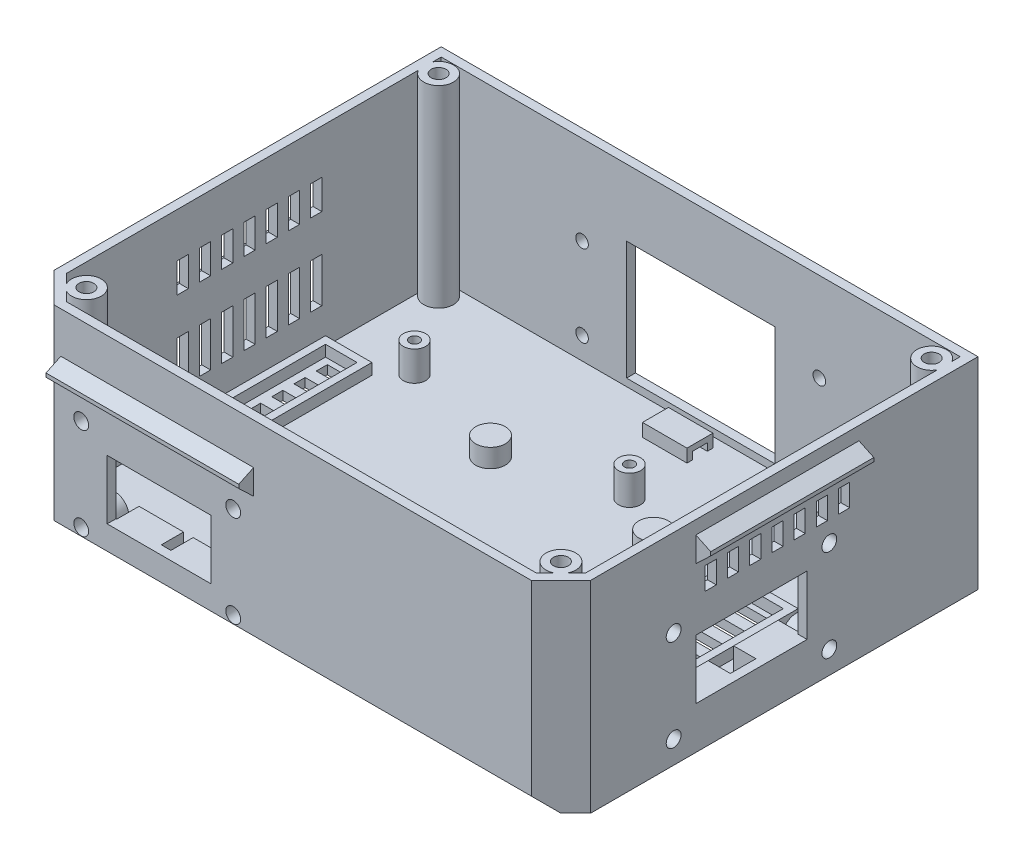
SolidWorks part; units mm, degrees
ref_plane "Front Plane" through (0, 0, 0) normal (0, 0, 1) x (1, 0, 0)
ref_plane "Top Plane" through (0, 0, 0) normal (0, 1, 0) x (1, 0, 0)
ref_plane "Right Plane" through (0, 0, 0) normal (1, 0, 0) x (0, 0, -1)
ref_plane "PZm28_4" through (0, -28.4, 0) normal (0, 1, 0) x (1, 0, 0)
sketch "Sketch1" plane through (0, -28.4, 0) normal (0, 1, 0) x (1, 0, 0)
  line L0 (-64.4, -124.4) -> (64.4, -124.4)
  line L1 (64.4, -124.4) -> (72.4, -116.4)
  line L2 (72.4, -116.4) -> (72.4, -11.9)
  line L3 (72.4, -11.9) -> (-72.4, -11.9)
  line L4 (-72.4, -11.9) -> (-72.4, -116.4)
  line L5 (-72.4, -116.4) -> (-64.4, -124.4)
extrude "Box Block" add sketch "Sketch1" along normal blind 54.4
sketch "Sketch2" plane through (0, 0, 0) normal (1, 0, 0) x (0, 0, -1)
  line L0 (-125.4, -23.4) -> (-119.4, -29.4)
  line L1 (-119.4, -29.4) -> (-125.4, -29.4)
  line L2 (-125.4, -29.4) -> (-125.4, -23.4)
extrude "Rear Bottom Facet" cut sketch "Sketch2" against normal through all and the other way through all
shell "Shell" thickness 2.4 removed face at (0, 26, 84.2333)
ref_plane "PY11_4" through (0, 0, 11.4) normal (0, 0, 1) x (1, 0, 0)
sketch "Sketch3" plane through (0, 0, 11.4) normal (0, 0, 1) x (1, 0, 0)
  line L0 (-20, -24) -> (20, -24)
  line L1 (20, -24) -> (20, 8)
  line L2 (20, 8) -> (-20, 8)
  line L3 (-20, 8) -> (-20, -24)
  circle A0 centre (-32, 2) radius 1.7
  circle A1 centre (32, 2) radius 1.7
  circle A2 centre (-32, -20) radius 1.7
  circle A3 centre (32, -20) radius 1.7
extrude "Cable Window and Flange Holes" cut sketch "Sketch3" along normal blind 3.4
ref_plane "PZm26_5" through (0, -26.5, 0) normal (0, 1, 0) x (1, 0, 0)
sketch "Sketch4" plane through (0, -26.5, 0) normal (0, 1, 0) x (1, 0, 0)
  circle A0 centre (-51.5, -89) radius 3
  circle A1 centre (6.5, -89) radius 3
  circle A2 centre (-51.5, -40) radius 3
  circle A3 centre (6.5, -40) radius 3
extrude "Pi Standoffs" add sketch "Sketch4" along normal blind 8.5
ref_plane "PZm28_9" through (0, -28.9, 0) normal (0, 1, 0) x (1, 0, 0)
sketch "Sketch5" plane through (0, -28.9, 0) normal (0, 1, 0) x (1, 0, 0)
  circle A0 centre (-51.5, -89) radius 1.35
  circle A1 centre (6.5, -89) radius 1.35
  circle A2 centre (-51.5, -40) radius 1.35
  circle A3 centre (6.5, -40) radius 1.35
extrude "Pi Screw Holes" cut sketch "Sketch5" along normal blind 11.4
sketch "Sketch6" plane through (0, -28.9, 0) normal (0, 1, 0) x (1, 0, 0)
  circle A0 centre (-51.5, -89) radius 2.75
  circle A1 centre (6.5, -89) radius 2.75
  circle A2 centre (-51.5, -40) radius 2.75
  circle A3 centre (6.5, -40) radius 2.75
extrude "Pi Counterbores" cut sketch "Sketch6" along normal blind 2.7
sketch "Sketch7" plane through (0, -26.5, 0) normal (0, 1, 0) x (1, 0, 0)
  circle A0 centre (-66.5, -18.5) radius 4
extrude "Lid Boss 1" add sketch "Sketch7" along normal blind 52.5
sketch "Sketch8" plane through (0, -26.5, 0) normal (0, 1, 0) x (1, 0, 0)
  circle A0 centre (66.5, -18.5) radius 4
extrude "Lid Boss 2" add sketch "Sketch8" along normal blind 52.5
sketch "Sketch9" plane through (0, -26.5, 0) normal (0, 1, 0) x (1, 0, 0)
  circle A0 centre (-64, -116) radius 4
extrude "Lid Boss 3" add sketch "Sketch9" along normal blind 52.5
sketch "Sketch10" plane through (0, -26.5, 0) normal (0, 1, 0) x (1, 0, 0)
  circle A0 centre (64, -116) radius 4
extrude "Lid Boss 4" add sketch "Sketch10" along normal blind 52.5
ref_plane "PZ20" through (0, 20, 0) normal (0, 1, 0) x (1, 0, 0)
sketch "Sketch11" plane through (0, 20, 0) normal (0, 1, 0) x (1, 0, 0)
  circle A0 centre (-66.5, -18.5) radius 2
  circle A1 centre (66.5, -18.5) radius 2
  circle A2 centre (-64, -116) radius 2
  circle A3 centre (64, -116) radius 2
extrude "Lid Insert Holes" cut sketch "Sketch11" along normal blind 6.5
sketch "Sketch12" plane through (0, -26.5, 0) normal (0, 1, 0) x (1, 0, 0)
  line L0 (38, -86) -> (58, -86)
  line L1 (58, -86) -> (58, -46)
  line L2 (58, -46) -> (38, -46)
  line L3 (38, -46) -> (38, -86)
  line L4 (40, -84) -> (56, -84)
  line L5 (56, -84) -> (56, -48)
  line L6 (56, -48) -> (40, -48)
  line L7 (40, -48) -> (40, -84)
extrude "Intake Upstand" add sketch "Sketch12" along normal blind 3.5
ref_plane "PZm29_4" through (0, -29.4, 0) normal (0, 1, 0) x (1, 0, 0)
sketch "Sketch13" plane through (0, -29.4, 0) normal (0, 1, 0) x (1, 0, 0)
  line L0 (42, -82.5) -> (54, -82.5)
  line L1 (54, -82.5) -> (54, -79.5)
  line L2 (54, -79.5) -> (42, -79.5)
  line L3 (42, -79.5) -> (42, -82.5)
  line L4 (42, -76.5) -> (54, -76.5)
  line L5 (54, -76.5) -> (54, -73.5)
  line L6 (54, -73.5) -> (42, -73.5)
  line L7 (42, -73.5) -> (42, -76.5)
  line L8 (42, -70.5) -> (54, -70.5)
  line L9 (54, -70.5) -> (54, -67.5)
  line L10 (54, -67.5) -> (42, -67.5)
  line L11 (42, -67.5) -> (42, -70.5)
  line L12 (42, -64.5) -> (54, -64.5)
  line L13 (54, -64.5) -> (54, -61.5)
  line L14 (54, -61.5) -> (42, -61.5)
  line L15 (42, -61.5) -> (42, -64.5)
  line L16 (42, -58.5) -> (54, -58.5)
  line L17 (54, -58.5) -> (54, -55.5)
  line L18 (54, -55.5) -> (42, -55.5)
  line L19 (42, -55.5) -> (42, -58.5)
  line L20 (42, -52.5) -> (54, -52.5)
  line L21 (54, -52.5) -> (54, -49.5)
  line L22 (54, -49.5) -> (42, -49.5)
  line L23 (42, -49.5) -> (42, -52.5)
extrude "Intake Slots" cut sketch "Sketch13" along normal blind 3.9
sketch "Sketch14" plane through (0, -26.5, 0) normal (0, 1, 0) x (1, 0, 0)
  line L0 (-69.5, -86) -> (-57, -86)
  line L1 (-57, -86) -> (-57, -46)
  line L2 (-57, -46) -> (-69.5, -46)
  line L3 (-69.5, -46) -> (-69.5, -86)
  line L4 (-67.5, -84) -> (-59, -84)
  line L5 (-59, -84) -> (-59, -48)
  line L6 (-59, -48) -> (-67.5, -48)
  line L7 (-67.5, -48) -> (-67.5, -84)
extrude "Floor Exhaust Upstand" add sketch "Sketch14" along normal blind 3.5
sketch "Sketch15" plane through (0, -29.4, 0) normal (0, 1, 0) x (1, 0, 0)
  line L0 (-65.5, -82.5) -> (-61, -82.5)
  line L1 (-61, -82.5) -> (-61, -79.5)
  line L2 (-61, -79.5) -> (-65.5, -79.5)
  line L3 (-65.5, -79.5) -> (-65.5, -82.5)
  line L4 (-65.5, -76.5) -> (-61, -76.5)
  line L5 (-61, -76.5) -> (-61, -73.5)
  line L6 (-61, -73.5) -> (-65.5, -73.5)
  line L7 (-65.5, -73.5) -> (-65.5, -76.5)
  line L8 (-65.5, -70.5) -> (-61, -70.5)
  line L9 (-61, -70.5) -> (-61, -67.5)
  line L10 (-61, -67.5) -> (-65.5, -67.5)
  line L11 (-65.5, -67.5) -> (-65.5, -70.5)
  line L12 (-65.5, -64.5) -> (-61, -64.5)
  line L13 (-61, -64.5) -> (-61, -61.5)
  line L14 (-61, -61.5) -> (-65.5, -61.5)
  line L15 (-65.5, -61.5) -> (-65.5, -64.5)
  line L16 (-65.5, -58.5) -> (-61, -58.5)
  line L17 (-61, -58.5) -> (-61, -55.5)
  line L18 (-61, -55.5) -> (-65.5, -55.5)
  line L19 (-65.5, -55.5) -> (-65.5, -58.5)
  line L20 (-65.5, -52.5) -> (-61, -52.5)
  line L21 (-61, -52.5) -> (-61, -49.5)
  line L22 (-61, -49.5) -> (-65.5, -49.5)
  line L23 (-65.5, -49.5) -> (-65.5, -52.5)
extrude "Floor Exhaust Slots" cut sketch "Sketch15" along normal blind 3.9
ref_plane "PXm72_9" through (-72.9, 0, 0) normal (1, 0, 0) x (0, 0, -1)
sketch "Sketch16" plane through (-72.9, 0, 0) normal (1, 0, 0) x (0, 0, -1)
  line L0 (-85.5, -16) -> (-82.5, -16)
  line L1 (-82.5, -16) -> (-82.5, -4)
  line L2 (-82.5, -4) -> (-85.5, -4)
  line L3 (-85.5, -4) -> (-85.5, -16)
  line L4 (-79.5, -16) -> (-76.5, -16)
  line L5 (-76.5, -16) -> (-76.5, -4)
  line L6 (-76.5, -4) -> (-79.5, -4)
  line L7 (-79.5, -4) -> (-79.5, -16)
  line L8 (-73.5, -16) -> (-70.5, -16)
  line L9 (-70.5, -16) -> (-70.5, -4)
  line L10 (-70.5, -4) -> (-73.5, -4)
  line L11 (-73.5, -4) -> (-73.5, -16)
  line L12 (-67.5, -16) -> (-64.5, -16)
  line L13 (-64.5, -16) -> (-64.5, -4)
  line L14 (-64.5, -4) -> (-67.5, -4)
  line L15 (-67.5, -4) -> (-67.5, -16)
  line L16 (-61.5, -16) -> (-58.5, -16)
  line L17 (-58.5, -16) -> (-58.5, -4)
  line L18 (-58.5, -4) -> (-61.5, -4)
  line L19 (-61.5, -4) -> (-61.5, -16)
  line L20 (-55.5, -16) -> (-52.5, -16)
  line L21 (-52.5, -16) -> (-52.5, -4)
  line L22 (-52.5, -4) -> (-55.5, -4)
  line L23 (-55.5, -4) -> (-55.5, -16)
  line L24 (-49.5, -16) -> (-46.5, -16)
  line L25 (-46.5, -16) -> (-46.5, -4)
  line L26 (-46.5, -4) -> (-49.5, -4)
  line L27 (-49.5, -4) -> (-49.5, -16)
extrude "Exhaust Vents" cut sketch "Sketch16" along normal blind 3.4
ref_plane "PY44" through (0, 0, 44) normal (0, 0, 1) x (1, 0, 0)
sketch "Sketch17" plane through (0, 0, 44) normal (0, 0, 1) x (1, 0, 0)
  line L0 (-72.2, -2.5) -> (-76.4, 1.5)
  line L1 (-76.4, 1.5) -> (-76.4, 2.5)
  line L2 (-76.4, 2.5) -> (-72.2, 4.5)
  line L3 (-72.2, 4.5) -> (-72.2, -2.5)
extrude "Exhaust Drip Ledge" add sketch "Sketch17" along normal blind 44
sketch "Sketch18" plane through (-72.9, 0, 0) normal (1, 0, 0) x (0, 0, -1)
  line L0 (-85.5, 6) -> (-82.5, 6)
  line L1 (-82.5, 6) -> (-82.5, 14)
  line L2 (-82.5, 14) -> (-85.5, 14)
  line L3 (-85.5, 14) -> (-85.5, 6)
  line L4 (-79.5, 6) -> (-76.5, 6)
  line L5 (-76.5, 6) -> (-76.5, 14)
  line L6 (-76.5, 14) -> (-79.5, 14)
  line L7 (-79.5, 14) -> (-79.5, 6)
  line L8 (-73.5, 6) -> (-70.5, 6)
  line L9 (-70.5, 6) -> (-70.5, 14)
  line L10 (-70.5, 14) -> (-73.5, 14)
  line L11 (-73.5, 14) -> (-73.5, 6)
  line L12 (-67.5, 6) -> (-64.5, 6)
  line L13 (-64.5, 6) -> (-64.5, 14)
  line L14 (-64.5, 14) -> (-67.5, 14)
  line L15 (-67.5, 14) -> (-67.5, 6)
  line L16 (-61.5, 6) -> (-58.5, 6)
  line L17 (-58.5, 6) -> (-58.5, 14)
  line L18 (-58.5, 14) -> (-61.5, 14)
  line L19 (-61.5, 14) -> (-61.5, 6)
  line L20 (-55.5, 6) -> (-52.5, 6)
  line L21 (-52.5, 6) -> (-52.5, 14)
  line L22 (-52.5, 14) -> (-55.5, 14)
  line L23 (-55.5, 14) -> (-55.5, 6)
  line L24 (-49.5, 6) -> (-46.5, 6)
  line L25 (-46.5, 6) -> (-46.5, 14)
  line L26 (-46.5, 14) -> (-49.5, 14)
  line L27 (-49.5, 14) -> (-49.5, 6)
extrude "Upper Vents L" cut sketch "Sketch18" along normal blind 3.4
sketch "Sketch19" plane through (0, 0, 44) normal (0, 0, 1) x (1, 0, 0)
  line L0 (-72.2, 15.5) -> (-76.4, 19.5)
  line L1 (-76.4, 19.5) -> (-76.4, 20.5)
  line L2 (-76.4, 20.5) -> (-72.2, 22.5)
  line L3 (-72.2, 22.5) -> (-72.2, 15.5)
extrude "Upper Drip Ledge L" add sketch "Sketch19" along normal blind 44
ref_plane "PX69_5" through (69.5, 0, 0) normal (1, 0, 0) x (0, 0, -1)
sketch "Sketch20" plane through (69.5, 0, 0) normal (1, 0, 0) x (0, 0, -1)
  line L0 (-85.5, 8) -> (-82.5, 8)
  line L1 (-82.5, 8) -> (-82.5, 14)
  line L2 (-82.5, 14) -> (-85.5, 14)
  line L3 (-85.5, 14) -> (-85.5, 8)
  line L4 (-79.5, 8) -> (-76.5, 8)
  line L5 (-76.5, 8) -> (-76.5, 14)
  line L6 (-76.5, 14) -> (-79.5, 14)
  line L7 (-79.5, 14) -> (-79.5, 8)
  line L8 (-73.5, 8) -> (-70.5, 8)
  line L9 (-70.5, 8) -> (-70.5, 14)
  line L10 (-70.5, 14) -> (-73.5, 14)
  line L11 (-73.5, 14) -> (-73.5, 8)
  line L12 (-67.5, 8) -> (-64.5, 8)
  line L13 (-64.5, 8) -> (-64.5, 14)
  line L14 (-64.5, 14) -> (-67.5, 14)
  line L15 (-67.5, 14) -> (-67.5, 8)
  line L16 (-61.5, 8) -> (-58.5, 8)
  line L17 (-58.5, 8) -> (-58.5, 14)
  line L18 (-58.5, 14) -> (-61.5, 14)
  line L19 (-61.5, 14) -> (-61.5, 8)
  line L20 (-55.5, 8) -> (-52.5, 8)
  line L21 (-52.5, 8) -> (-52.5, 14)
  line L22 (-52.5, 14) -> (-55.5, 14)
  line L23 (-55.5, 14) -> (-55.5, 8)
  line L24 (-49.5, 8) -> (-46.5, 8)
  line L25 (-46.5, 8) -> (-46.5, 14)
  line L26 (-46.5, 14) -> (-49.5, 14)
  line L27 (-49.5, 14) -> (-49.5, 8)
extrude "Upper Vents R" cut sketch "Sketch20" along normal blind 3.4
sketch "Sketch21" plane through (0, 0, 44) normal (0, 0, 1) x (1, 0, 0)
  line L0 (72.2, 15.5) -> (76.4, 19.5)
  line L1 (76.4, 19.5) -> (76.4, 20.5)
  line L2 (76.4, 20.5) -> (72.2, 22.5)
  line L3 (72.2, 22.5) -> (72.2, 15.5)
extrude "Upper Drip Ledge R" add sketch "Sketch21" along normal blind 44
ref_plane "PY121_5" through (0, 0, 121.5) normal (0, 0, 1) x (1, 0, 0)
sketch "Sketch22" plane through (0, 0, 121.5) normal (0, 0, 1) x (1, 0, 0)
  line L0 (-50, -18) -> (-22, -18)
  line L1 (-22, -18) -> (-22, -2)
  line L2 (-22, -2) -> (-50, -2)
  line L3 (-50, -2) -> (-50, -18)
extrude "Rear Port Opening" cut sketch "Sketch22" along normal blind 3.4
ref_plane "PY115_5" through (0, 0, 115.5) normal (0, 0, 1) x (1, 0, 0)
sketch "Sketch23" plane through (0, 0, 115.5) normal (0, 0, 1) x (1, 0, 0)
  circle A0 centre (-57, -22.3) radius 4
  circle A1 centre (-57, 2.5) radius 4
  circle A2 centre (-16, -22.3) radius 4
  circle A3 centre (-16, 2.5) radius 4
extrude "Rear Port Bosses" add sketch "Sketch23" along normal blind 6.6
ref_plane "PY117_9" through (0, 0, 117.9) normal (0, 0, 1) x (1, 0, 0)
sketch "Sketch24" plane through (0, 0, 117.9) normal (0, 0, 1) x (1, 0, 0)
  circle A0 centre (-57, -22.3) radius 2
  circle A1 centre (-57, 2.5) radius 2
  circle A2 centre (-16, -22.3) radius 2
  circle A3 centre (-16, 2.5) radius 2
extrude "Rear Port Insert Holes" cut sketch "Sketch24" along normal blind 7
ref_plane "PXm62_5" through (-62.5, 0, 0) normal (1, 0, 0) x (0, 0, -1)
sketch "Sketch25" plane through (-62.5, 0, 0) normal (1, 0, 0) x (0, 0, -1)
  line L0 (-124.2, 8) -> (-128.4, 12)
  line L1 (-128.4, 12) -> (-128.4, 13)
  line L2 (-128.4, 13) -> (-124.2, 15)
  line L3 (-124.2, 15) -> (-124.2, 8)
extrude "Rear Port Drip Ledge" add sketch "Sketch25" along normal blind 52
sketch "Sketch26" plane through (0, -26.5, 0) normal (0, 1, 0) x (1, 0, 0)
  line L0 (-49.8, -122.1) -> (-37.8, -122.1)
  line L1 (-37.8, -122.1) -> (-37.8, -116)
  line L2 (-37.8, -116) -> (-49.8, -116)
  line L3 (-49.8, -116) -> (-49.8, -122.1)
extrude "Rear Tie Block usbc" add sketch "Sketch26" along normal blind 8.5
ref_plane "PXm50_8" through (-50.8, 0, 0) normal (1, 0, 0) x (0, 0, -1)
sketch "Sketch27" plane through (-50.8, 0, 0) normal (1, 0, 0) x (0, 0, -1)
  line L0 (-120.5, -24.5) -> (-117.5, -24.5)
  line L1 (-117.5, -24.5) -> (-117.5, -22.5)
  line L2 (-117.5, -22.5) -> (-120.5, -22.5)
  line L3 (-120.5, -22.5) -> (-120.5, -24.5)
extrude "Rear Tie Tunnel usbc" cut sketch "Sketch27" along normal blind 14
sketch "Sketch28" plane through (0, -26.5, 0) normal (0, 1, 0) x (1, 0, 0)
  line L0 (-35.2, -122.1) -> (-23.2, -122.1)
  line L1 (-23.2, -122.1) -> (-23.2, -116)
  line L2 (-23.2, -116) -> (-35.2, -116)
  line L3 (-35.2, -116) -> (-35.2, -122.1)
extrude "Rear Tie Block hdmi" add sketch "Sketch28" along normal blind 8.5
ref_plane "PXm36_2" through (-36.2, 0, 0) normal (1, 0, 0) x (0, 0, -1)
sketch "Sketch29" plane through (-36.2, 0, 0) normal (1, 0, 0) x (0, 0, -1)
  line L0 (-120.5, -24.5) -> (-117.5, -24.5)
  line L1 (-117.5, -24.5) -> (-117.5, -22.5)
  line L2 (-117.5, -22.5) -> (-120.5, -22.5)
  line L3 (-120.5, -22.5) -> (-120.5, -24.5)
extrude "Rear Tie Tunnel hdmi" cut sketch "Sketch29" along normal blind 14
sketch "Sketch30" plane through (69.5, 0, 0) normal (1, 0, 0) x (0, 0, -1)
  line L0 (-88, -17) -> (-58, -17)
  line L1 (-58, -17) -> (-58, -1)
  line L2 (-58, -1) -> (-88, -1)
  line L3 (-88, -1) -> (-88, -17)
extrude "Side Port Opening" cut sketch "Sketch30" along normal blind 3.4
ref_plane "PX63_5" through (63.5, 0, 0) normal (1, 0, 0) x (0, 0, -1)
sketch "Sketch31" plane through (63.5, 0, 0) normal (1, 0, 0) x (0, 0, -1)
  circle A0 centre (-94, -22.3) radius 4
  circle A1 centre (-94, 2.5) radius 4
  circle A2 centre (-52, -22.3) radius 4
  circle A3 centre (-52, 2.5) radius 4
extrude "Side Port Bosses" add sketch "Sketch31" along normal blind 6.6
ref_plane "PX65_9" through (65.9, 0, 0) normal (1, 0, 0) x (0, 0, -1)
sketch "Sketch32" plane through (65.9, 0, 0) normal (1, 0, 0) x (0, 0, -1)
  circle A0 centre (-94, -22.3) radius 2
  circle A1 centre (-94, 2.5) radius 2
  circle A2 centre (-52, -22.3) radius 2
  circle A3 centre (-52, 2.5) radius 2
extrude "Side Port Insert Holes" cut sketch "Sketch32" along normal blind 7
sketch "Sketch33" plane through (0, -26.5, 0) normal (0, 1, 0) x (1, 0, 0)
  line L0 (64, -88.3) -> (70.1, -88.3)
  line L1 (70.1, -88.3) -> (70.1, -76.3)
  line L2 (70.1, -76.3) -> (64, -76.3)
  line L3 (64, -76.3) -> (64, -88.3)
extrude "Side Tie Block eth" add sketch "Sketch33" along normal blind 9.5
ref_plane "PY75_3" through (0, 0, 75.3) normal (0, 0, 1) x (1, 0, 0)
sketch "Sketch34" plane through (0, 0, 75.3) normal (0, 0, 1) x (1, 0, 0)
  line L0 (65.5, -24.5) -> (68.5, -24.5)
  line L1 (68.5, -24.5) -> (68.5, -22.5)
  line L2 (68.5, -22.5) -> (65.5, -22.5)
  line L3 (65.5, -22.5) -> (65.5, -24.5)
extrude "Side Tie Tunnel eth" cut sketch "Sketch34" along normal blind 14
sketch "Sketch35" plane through (0, -26.5, 0) normal (0, 1, 0) x (1, 0, 0)
  line L0 (64, -69.4) -> (70.1, -69.4)
  line L1 (70.1, -69.4) -> (70.1, -57.4)
  line L2 (70.1, -57.4) -> (64, -57.4)
  line L3 (64, -57.4) -> (64, -69.4)
extrude "Side Tie Block usba" add sketch "Sketch35" along normal blind 9.5
ref_plane "PY56_4" through (0, 0, 56.4) normal (0, 0, 1) x (1, 0, 0)
sketch "Sketch36" plane through (0, 0, 56.4) normal (0, 0, 1) x (1, 0, 0)
  line L0 (65.5, -24.5) -> (68.5, -24.5)
  line L1 (68.5, -24.5) -> (68.5, -22.5)
  line L2 (68.5, -22.5) -> (65.5, -22.5)
  line L3 (65.5, -22.5) -> (65.5, -24.5)
extrude "Side Tie Tunnel usba" cut sketch "Sketch36" along normal blind 14
sketch "Sketch37" plane through (0, -26.5, 0) normal (0, 1, 0) x (1, 0, 0)
  line L0 (-6, -24) -> (6, -24)
  line L1 (6, -24) -> (6, -17)
  line L2 (6, -17) -> (-6, -17)
  line L3 (-6, -17) -> (-6, -24)
extrude "Bundle Tie Anchor" add sketch "Sketch37" along normal blind 4
ref_plane "PXm7" through (-7, 0, 0) normal (1, 0, 0) x (0, 0, -1)
sketch "Sketch38" plane through (-7, 0, 0) normal (1, 0, 0) x (0, 0, -1)
  line L0 (-22.5, -26) -> (-18.5, -26)
  line L1 (-18.5, -26) -> (-18.5, -24)
  line L2 (-18.5, -24) -> (-22.5, -24)
  line L3 (-22.5, -24) -> (-22.5, -26)
extrude "Bundle Tie Slot" cut sketch "Sketch38" along normal blind 14
sketch "Sketch39" plane through (0, -26.5, 0) normal (0, 1, 0) x (1, 0, 0)
  circle A0 centre (-22, -91) radius 4
  circle A1 centre (-22, -49) radius 4
  circle A2 centre (22, -91) radius 4
  circle A3 centre (22, -49) radius 4
extrude "Rail Plate Bosses" add sketch "Sketch39" along normal blind 5.5
sketch "Sketch40" plane through (0, -28.9, 0) normal (0, 1, 0) x (1, 0, 0)
  circle A0 centre (-22, -91) radius 2
  circle A1 centre (-22, -49) radius 2
  circle A2 centre (22, -91) radius 2
  circle A3 centre (22, -49) radius 2
extrude "Rail Insert Holes" cut sketch "Sketch40" along normal blind 6.5
equation "\"BOARD_REAR\" = 86.0"
equation "\"BOARD_FRONT\" = 41.0"
equation "\"BOARD_END\" = 22.0"
equation "\"BOARD_ANGLED\" = 30.0"
equation "\"BOARD_DEPTH\" = 41.8431"
equation "\"PCB_T\" = 1.6"
equation "\"ABOVE_PCB\" = 14.0"
equation "\"BELOW_PCB\" = 6.0"
equation "\"MID_PARTS_H\" = 9.0"
equation "\"BOARD_HOLE_PILOT\" = 1.6"
equation "\"J2_X\" = 19.0"
equation "\"DUPONT_DROP\" = 14.0"
equation "\"BEND_R\" = 5.0"
equation "\"BOARD_GAP\" = 3.0"
equation "\"TOF_FOV\" = 25.0"
equation "\"TOF_MARGIN_DEG\" = 5.0"
equation "\"TOF_WIN_MARGIN\" = 1.0"
equation "\"TOF_Z\" = 9.0"
equation "\"TOF_SIDE_BEARING\" = 90.0"
equation "\"TOF_CONE_LEN\" = 70.0"
equation "\"CAM_W\" = 29.2"
equation "\"CAM_H\" = 28.2"
equation "\"CAM_D\" = 12.35"
equation "\"CAM_FRONT_Y\" = 43.0"
equation "\"CAM_BOTTOM_Z\" = 17.0"
equation "\"CAM_LENS_UP\" = 11.6"
equation "\"CAM_LENS_OPEN\" = 9.6"
equation "\"CAM_HFOV\" = 53.5"
equation "\"CAM_VFOV\" = 41.41"
equation "\"CAM_FOV_MARGIN\" = 3.0"
equation "\"CAM_FIT\" = 0.3"
equation "\"RIBBON_W\" = 16.0"
equation "\"RIBBON_T\" = 0.3"
equation "\"RIBBON_LEN\" = 150.0"
equation "\"RIBBON_EXIT_Y\" = 35.0"
equation "\"WALL\" = 2.4"
equation "\"HEAD_X\" = 48.4"
equation "\"HEAD_REAR_Y\" = -11.9"
equation "\"CAM_FOAM\" = 2.8"
equation "\"HEAD_FRONT_Y\" = 48.2"
equation "\"HEAD_TOP_Z\" = 50.6"
equation "\"HEAD_BOT_Z\" = -28.4"
equation "\"HEAD_SPLIT_Z\" = -4.0"
equation "\"SKIRT_T\" = 1.2"
equation "\"SKIRT_H\" = 3.0"
equation "\"SKIRT_FIT\" = 0.3"
equation "\"VISOR\" = 7.8"
equation "\"VISOR_Z\" = 40.0"
equation "\"ROOF_SLOPE_Y\" = 40.0"
equation "\"ROOF_CHAMFER\" = 10.0"
equation "\"REAR_CHAMFER\" = 10.0"
equation "\"CORNER_CHAMFER\" = 6.0"
equation "\"LOWER_SIDE_FACET\" = 6.0"
equation "\"LIGHTBAR_DEPTH\" = 1.0"
equation "\"HOOD_Z\" = 14.0"
equation "\"HOOD_L\" = 6.0"
equation "\"SIDE_HOOD_L\" = 4.0"
equation "\"INSERT_M3_D\" = 4.0"
equation "\"INSERT_M3_L\" = 6.0"
equation "\"M3_CLEAR\" = 3.4"
equation "\"M2_PILOT\" = 1.6"
equation "\"M25_PILOT\" = 2.2"
equation "\"BOX_X\" = 72.4"
equation "\"BOX_FRONT_Y\" = -11.9"
equation "\"BOX_REAR_Y\" = -124.4"
equation "\"BOX_BOT_Z\" = -28.4"
equation "\"BOX_TOP_Z\" = 26.0"
equation "\"LID_T\" = 2.4"
equation "\"LID_SKIRT\" = 1.6"
equation "\"LID_TONGUE_H\" = 3.0"
equation "\"LID_FIT\" = 0.3"
equation "\"PI_STANDOFF\" = 8.0"
equation "\"BOX_REAR_CHAMFER\" = 8.0"
equation "\"BOX_REAR_FACET\" = 4.0"
equation "\"VENT_UPSTAND\" = 3.0"
equation "\"TUBE_D\" = 22.2"
equation "\"TUBE_LINER\" = 1.0"
equation "\"MOUNT_Y\" = -70.0"
equation "\"RAIL_W\" = 30.0"
equation "\"RAIL_W2\" = 38.0"
equation "\"RAIL_H\" = 6.0"
equation "\"SLIDE\" = 0.3"
equation "\"STOP_T\" = 6.0"
equation "\"CLAMP_W\" = 40.0"
equation "\"CLAMP_HALF\" = 20.0"
equation "\"CLAMP_DROP\" = 12.0"
equation "\"CAP_T\" = 12.0"
equation "\"CLAMP_BOLT_OFF\" = 16.6"
equation "\"M5_INSERT_D\" = 6.4"
equation "\"M5_CLEAR\" = 5.5"
equation "\"LOCK_D\" = 3.3"
equation "\"POD_TILT_DEG\" = 0.0"
equation "\"PRINT_LIMIT\" = 180.0"
equation "\"PI5_L\" = 85.0"
equation "\"PI5_W\" = 56.0"
equation "\"PI5_T\" = 1.6"
equation "\"PI5_USBC_BX\" = 11.2"
equation "\"PI5_ETH_BY\" = 10.2"
equation "\"PI5_PORT_OVERHANG\" = 3.0"
equation "\"PI5_FPC_H\" = 5.0"
equation "\"PI5_FPC_USE\" = 0.0"
equation "\"PI5_PIN1_BX\" = 8.37"
equation "\"HEADER_BASE_H\" = 2.5"
equation "\"DUPONT_L\" = 14.0"
equation "\"PI5_UNDERSIDE\" = 1.5"
equation "\"COOLER_H\" = 15.0"
equation "\"HAT_W\" = 65.0"
equation "\"HAT_D\" = 56.5"
equation "\"HAT_T\" = 1.6"
equation "\"HAT_SPACER\" = 16.0"
equation "\"HAILO_H\" = 10.0"
equation "\"STACK_PINS_H\" = 6.0"
equation "\"DUPONT_SEAT\" = 0.5"
equation "\"PCIE_FFC_LOOP\" = 6.0"
equation "\"HAILO_AIR_GAP_MIN\" = 8.0"
equation "\"M25_CLEAR\" = 2.7"
equation "\"PI_X0\" = -55.0"
equation "\"PI_Y1\" = -36.5"
equation "\"PI_Y0\" = -92.5"
equation "\"BOX_LEN\" = 112.5"
equation "\"COVER_T\" = 3.0"
equation "\"COVER_TOP_Z\" = 6.5"
equation "\"SIDE_LEDGE_Z\" = -2.5"
equation "\"UPPER_LEDGE_Z\" = 15.5"
equation "\"REAR_LEDGE_Z\" = 8.0"
equation "\"LEDGE_L\" = 4.0"
equation "\"RIBBON_W_PI\" = 11.5"
equation "\"RIBBON_RUN_Z\" = 12.0"
equation "\"RIBBON_SPEC_LEN\" = 200.0"
